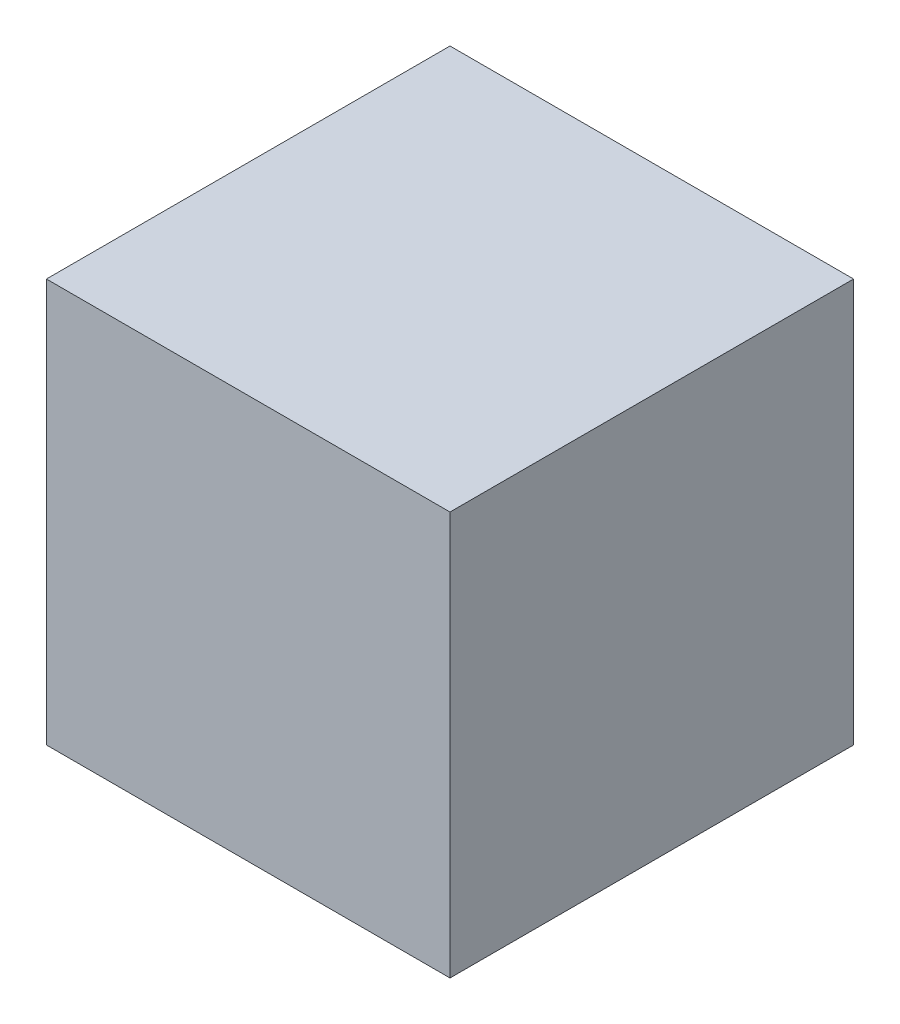
SolidWorks part; units mm, degrees
material "PE Low Density Film"
ref_plane "Front Plane" through (0, 0, 0) normal (0, 0, 1) x (1, 0, 0)
ref_plane "Top Plane" through (0, 0, 0) normal (0, 1, 0) x (1, 0, 0)
ref_plane "Right Plane" through (0, 0, 0) normal (1, 0, 0) x (0, 0, -1)
sketch "Sketch1" plane through (0, 0, 0) normal (0, 1, 0) x (1, 0, 0)
  line L1 (15, -15) -> (-15, -15)
  line L2 (15, -15) -> (15, 15)
  line L3 (15, 15) -> (-15, 15)
  line L4 (-15, -15) -> (-15, 15)
  line L5 (15, -15) -> (-15, 15) construction
  line L6 (15, 15) -> (-15, -15) construction
  point P0 (0, 0)
  dimension "D1" = 30
  dimension "D2" = 30
extrude "Boss-Extrude1" add sketch "Sketch1" along normal blind 15 and the other way blind 15
